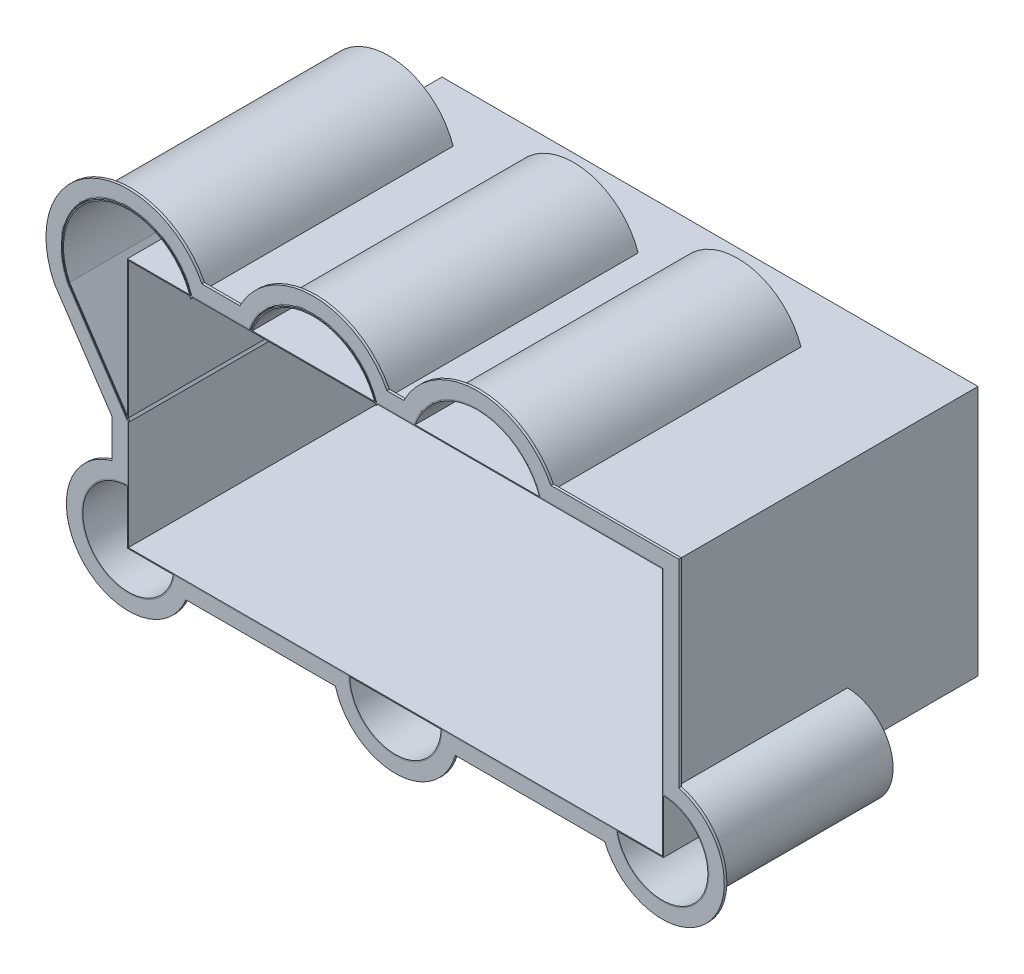
SolidWorks part; units mm, degrees
ref_plane "Front Plane" through (0, 0, 0) normal (0, 0, 1) x (1, 0, 0)
ref_plane "Top Plane" through (0, 0, 0) normal (0, 1, 0) x (1, 0, 0)
ref_plane "Right Plane" through (0, 0, 0) normal (1, 0, 0) x (0, 0, -1)
sketch "body " plane through (0, 0, 0) normal (0, 0, 1) x (1, 0, 0)
  line L0 (-4198.5075, 0) -> (2630, 0) construction
  line L1 (0, 1904.4776) -> (0, 1377) construction
  line L2 (-182.0761, 1377) -> (182.0761, 1377) construction
  line L3 (-2004.5761, 1377) -> (-1432.9239, 1377) construction
  line L4 (-2642, 0) -> (-2642, -552.1829) construction
  line L5 (-2174.5168, -1097) -> (-461.8441, -1097) construction
  line L6 (2642, 1377) -> (2642, -552.1829) construction
  line L7 (1432.9239, 1377) -> (2642, 1377) construction
  line L8 (461.8441, -1097) -> (2174.5168, -1097) construction
  line L9 (-3228.6495, 877.4) -> (-2642, 0) construction
  line L10 (-3359.2206, 802.8148) -> (-2792, -45.5271)
  line L11 (-2792, -45.5271) -> (-2792, -424.1059)
  line L12 (-2063.0892, -1247) -> (-590.1695, -1247)
  line L13 (590.1695, -1247) -> (2063.0892, -1247)
  line L14 (2792, 1527) -> (2792, -424.1059)
  line L15 (1531.8307, 1527) -> (2792, 1527)
  line L16 (-83.1693, 1527) -> (83.1693, 1527)
  line L17 (-1905.6693, 1527) -> (-1531.8307, 1527)
  line L18 (-4764.719, 1972) -> (6902.6993, 1972) construction
  line L19 (0, -1697) -> (4849.5432, -1697) construction
  line L20 (-4553.6407, -1626) -> (3482.8368, -1626) construction
  line L21 (-3442, 2950.9542) -> (-3442, -552.1829) construction
  line L22 (-2184.6364, -1085) -> (-450, -1085)
  line L23 (450, -1085) -> (2184.6364, -1085)
  line L24 (2630, 1365) -> (2630, -564.0011)
  line L25 (1424.3266, 1365) -> (2630, 1365)
  line L26 (-190.6734, 1365) -> (190.6734, 1365)
  line L27 (-2013.1734, 1365) -> (-1424.3266, 1365)
  line L28 (-3218.1761, 883.3254) -> (-2630, 3.6422)
  line L29 (-2630, 3.6422) -> (-2630, -564.0011)
  line L30 (-2630, 3.6422) -> (-2630, 1365) construction
  line L31 (-2630, -564.0011) -> (-2630, -1085) construction
  line L32 (-2630, -1085) -> (-2184.6364, -1085) construction
  line L33 (-2630, 1365) -> (2792, 1365) construction
  line L34 (2184.6364, -1085) -> (2630, -1085) construction
  line L35 (2630, -1085) -> (2630, -564.0011) construction
  line L36 (0, 1365) -> (0, -1535) construction
  line L37 (2642, 0) -> (4111.9403, 0) construction
  line L38 (0, -1547) -> (0, -2034.3284) construction
  line L39 (-2640, 0.607) -> (-2640, -554.1315)
  line L40 (-2176.1877, -1095) -> (-459.8913, -1095)
  line L41 (459.8913, -1095) -> (2176.1877, -1095)
  line L42 (2640, 1375) -> (2640, -554.1315)
  line L43 (1431.4992, 1375) -> (2640, 1375)
  line L44 (-183.5008, 1375) -> (183.5008, 1375)
  line L45 (-2006.0008, 1375) -> (-1431.4992, 1375)
  line L46 (-3226.9043, 878.388) -> (-2640, 0.607)
  line L51 (-450, -1085) -> (450, -1085) construction
  arc A0 (-182.0761, 1377) -> (-1432.9239, 1377) centre (-807.5, 1160) ccw construction
  arc A1 (1432.9239, 1377) -> (182.0761, 1377) centre (807.5, 1160) ccw construction
  arc A2 (-2642, -552.1829) -> (-2174.5168, -1097) centre (-2629, -1014) ccw construction
  arc A3 (-461.8441, -1097) -> (461.8441, -1097) centre (0, -1085) ccw construction
  arc A4 (2174.5168, -1097) -> (2642, -552.1829) centre (2629, -1014) ccw construction
  arc A5 (-2004.5761, 1377) -> (-3228.6495, 877.4) centre (-2630, 1160) ccw construction
  arc A6 (-1905.6693, 1527) -> (-3359.2206, 802.8148) centre (-2630, 1160) ccw
  arc A7 (-2792, -424.1059) -> (-2063.0892, -1247) centre (-2629, -1014) ccw
  arc A8 (-590.1695, -1247) -> (590.1695, -1247) centre (0, -1085) ccw
  arc A9 (2063.0892, -1247) -> (2792, -424.1059) centre (2629, -1014) ccw
  arc A10 (1531.8307, 1527) -> (83.1693, 1527) centre (807.5, 1160) ccw
  arc A11 (-83.1693, 1527) -> (-1531.8307, 1527) centre (-807.5, 1160) ccw
  arc A12 (-2630, -564.0011) -> (-2184.6364, -1085) centre (-2629, -1014) ccw
  arc A13 (-450, -1085) -> (450, -1085) centre (0, -1085) ccw
  arc A14 (2184.6364, -1085) -> (2630, -564.0011) centre (2629, -1014) ccw
  arc A15 (1424.3266, 1365) -> (190.6734, 1365) centre (807.5, 1160) ccw
  arc A16 (-190.6734, 1365) -> (-1424.3266, 1365) centre (-807.5, 1160) ccw
  arc A17 (-2013.1734, 1365) -> (-3218.1761, 883.3254) centre (-2630, 1160) ccw
  arc A18 (-2640, -554.1315) -> (-2176.1877, -1095) centre (-2629, -1014) ccw
  arc A19 (-459.8913, -1095) -> (459.8913, -1095) centre (0, -1085) ccw
  arc A20 (2176.1877, -1095) -> (2640, -554.1315) centre (2629, -1014) ccw
  arc A21 (1431.4992, 1375) -> (183.5008, 1375) centre (807.5, 1160) ccw
  arc A22 (-183.5008, 1375) -> (-1431.4992, 1375) centre (-807.5, 1160) ccw
  arc A23 (-2006.0008, 1375) -> (-3226.9043, 878.388) centre (-2630, 1160) ccw
  dimension "D2" = 662
  dimension "D3" = 662
  dimension "D11" = 462
  dimension "D15" = 462
  dimension "D17" = 462
  dimension "D25" = 662
  dimension "D41" = 612
  dimension "D54" = 450
  dimension "D57" = 450
  dimension "D58" = 450
  dimension "D59" = 650
  dimension "D60" = 650
  dimension "D1" = 1160
  dimension "D4" = 807.5
  dimension "D5" = 807.5
  dimension "D6" = 1377
  dimension "D7" = 1834.5
  dimension "D8" = 1209.0761
  dimension "D9" = 1097
  dimension "D10" = 1014
  dimension "D12" = 2629
  dimension "D13" = 2629
  dimension "D14" = 2642
  dimension "D16" = 1085
  dimension "D18" = 461.8441
  dimension "D19" = 461.8441
  dimension "D20" = 364.1523
  dimension "D21" = 552.1829
  dimension "D22" = 1712.6726
  dimension "D23" = 1712.6726
  dimension "D24" = 1822.5
  dimension "D26" = 282.6
  dimension "D27" = 598.6495
  dimension "D28" = 1055.4565
  dimension "D29" = 552.1829
  dimension "D30" = 217
  dimension "D31" = 571.6523
  dimension "D33" = 1697
  dimension "D34" = 1626
  dimension "D35" = 1972
  dimension "D36" = 3598
  dimension "D37" = 1972
  dimension "D38" = 1626
  dimension "D39" = 3669
  dimension "D40" = 6234
  dimension "D42" = 83
  dimension "D43" = 1472.9198
  dimension "D44" = 1472.9198
  dimension "D45" = 424.1059
  dimension "D46" = 1951.1059
  dimension "D47" = 1260.1693
  dimension "D48" = 166.3385
  dimension "D49" = 373.8385
  dimension "D50" = 1020.5015
  dimension "D51" = 2642
  dimension "D52" = 1014
  dimension "D55" = 2630
  dimension "D56" = 2630
  dimension "D61" = 1365
  dimension "D62" = 33.768
  dimension "D63" = 1085
  dimension "D64" = 10
  dimension "D32" = 150
  dimension "D53" = 12
sketch "curb" plane through (0, 0, 0) normal (0, 0, 1) x (1, 0, 0)
  line L0 (-4198.5075, 0) -> (2630, 0) construction
  line L1 (0, 1904.4776) -> (0, 1377) construction
  line L2 (-182.0761, 1377) -> (182.0761, 1377) construction
  line L3 (-2004.5761, 1377) -> (-1432.9239, 1377) construction
  line L4 (-2642, 0) -> (-2642, -552.1829) construction
  line L5 (-2174.5168, -1097) -> (-461.8441, -1097) construction
  line L6 (2642, 1377) -> (2642, -552.1829) construction
  line L7 (1432.9239, 1377) -> (2642, 1377) construction
  line L8 (461.8441, -1097) -> (2174.5168, -1097) construction
  line L9 (-3228.6495, 877.4) -> (-2642, 0) construction
  line L10 (-3359.2206, 802.8148) -> (-2792, -45.5271)
  line L11 (-2792, -45.5271) -> (-2792, -424.1059)
  line L12 (-2063.0892, -1247) -> (-590.1695, -1247)
  line L13 (590.1695, -1247) -> (2063.0892, -1247)
  line L14 (2792, 1527) -> (2792, -424.1059)
  line L15 (1531.8307, 1527) -> (2792, 1527)
  line L16 (-83.1693, 1527) -> (83.1693, 1527)
  line L17 (-1905.6693, 1527) -> (-1531.8307, 1527)
  line L18 (-4764.719, 1972) -> (6902.6993, 1972) construction
  line L19 (0, -1697) -> (4849.5432, -1697) construction
  line L20 (-4553.6407, -1626) -> (3482.8368, -1626) construction
  line L21 (-3442, 2950.9542) -> (-3442, -552.1829) construction
  line L22 (-2184.6364, -1085) -> (-450, -1085)
  line L23 (450, -1085) -> (2184.6364, -1085)
  line L24 (2630, 1365) -> (2630, -564.0011)
  line L25 (1424.3266, 1365) -> (2630, 1365)
  line L26 (-190.6734, 1365) -> (190.6734, 1365)
  line L27 (-2013.1734, 1365) -> (-1424.3266, 1365)
  line L28 (-3218.1761, 883.3254) -> (-2630, 3.6422)
  line L29 (-2630, 3.6422) -> (-2630, -564.0011)
  line L30 (-2630, 3.6422) -> (-2630, 1365) construction
  line L31 (-2630, -564.0011) -> (-2630, -1085) construction
  line L32 (-2630, -1085) -> (-2184.6364, -1085) construction
  line L33 (-2630, 1365) -> (2792, 1365) construction
  line L34 (2184.6364, -1085) -> (2630, -1085) construction
  line L35 (2630, -1085) -> (2630, -564.0011) construction
  line L36 (0, 1365) -> (0, -1535) construction
  line L37 (2642, 0) -> (4111.9403, 0) construction
  line L38 (0, -1547) -> (0, -2034.3284) construction
  line L39 (-2640, 0.607) -> (-2640, -554.1315)
  line L40 (-2176.1877, -1095) -> (-459.8913, -1095)
  line L41 (459.8913, -1095) -> (2176.1877, -1095)
  line L42 (2640, 1375) -> (2640, -554.1315)
  line L43 (1431.4992, 1375) -> (2640, 1375)
  line L44 (-183.5008, 1375) -> (183.5008, 1375)
  line L45 (-2006.0008, 1375) -> (-1431.4992, 1375)
  line L46 (-3226.9043, 878.388) -> (-2640, 0.607)
  line L47 (0, 0) -> (270.3964, 194.0028)
  line L48 (270.3964, 194.0028) -> (0, 194.0028)
  line L49 (0, 194.0028) -> (270.3964, 0)
  line L50 (270.3964, 0) -> (270.3964, 194.0028)
  arc A0 (-182.0761, 1377) -> (-1432.9239, 1377) centre (-807.5, 1160) ccw construction
  arc A1 (1432.9239, 1377) -> (182.0761, 1377) centre (807.5, 1160) ccw construction
  arc A2 (-2642, -552.1829) -> (-2174.5168, -1097) centre (-2629, -1014) ccw construction
  arc A3 (-461.8441, -1097) -> (461.8441, -1097) centre (0, -1085) ccw construction
  arc A4 (2174.5168, -1097) -> (2642, -552.1829) centre (2629, -1014) ccw construction
  arc A5 (-2004.5761, 1377) -> (-3228.6495, 877.4) centre (-2630, 1160) ccw construction
  arc A6 (-1905.6693, 1527) -> (-3359.2206, 802.8148) centre (-2630, 1160) ccw
  arc A7 (-2792, -424.1059) -> (-2063.0892, -1247) centre (-2629, -1014) ccw
  arc A8 (-590.1695, -1247) -> (590.1695, -1247) centre (0, -1085) ccw
  arc A9 (2063.0892, -1247) -> (2792, -424.1059) centre (2629, -1014) ccw
  arc A10 (1531.8307, 1527) -> (83.1693, 1527) centre (807.5, 1160) ccw
  arc A11 (-83.1693, 1527) -> (-1531.8307, 1527) centre (-807.5, 1160) ccw
  arc A12 (-2630, -564.0011) -> (-2184.6364, -1085) centre (-2629, -1014) ccw
  arc A13 (-450, -1085) -> (450, -1085) centre (0, -1085) ccw
  arc A14 (2184.6364, -1085) -> (2630, -564.0011) centre (2629, -1014) ccw
  arc A15 (1424.3266, 1365) -> (190.6734, 1365) centre (807.5, 1160) ccw
  arc A16 (-190.6734, 1365) -> (-1424.3266, 1365) centre (-807.5, 1160) ccw
  arc A17 (-2013.1734, 1365) -> (-3218.1761, 883.3254) centre (-2630, 1160) ccw
  arc A18 (-2640, -554.1315) -> (-2176.1877, -1095) centre (-2629, -1014) ccw
  arc A19 (-459.8913, -1095) -> (459.8913, -1095) centre (0, -1085) ccw
  arc A20 (2176.1877, -1095) -> (2640, -554.1315) centre (2629, -1014) ccw
  arc A21 (1431.4992, 1375) -> (183.5008, 1375) centre (807.5, 1160) ccw
  arc A22 (-183.5008, 1375) -> (-1431.4992, 1375) centre (-807.5, 1160) ccw
  arc A23 (-2006.0008, 1375) -> (-3226.9043, 878.388) centre (-2630, 1160) ccw
  point P107 (0, 0)
  dimension "D2" = 662
  dimension "D3" = 662
  dimension "D11" = 462
  dimension "D15" = 462
  dimension "D17" = 462
  dimension "D25" = 662
  dimension "D41" = 612
  dimension "D54" = 450
  dimension "D57" = 450
  dimension "D58" = 450
  dimension "D59" = 650
  dimension "D60" = 650
  dimension "D1" = 1160
  dimension "D4" = 807.5
  dimension "D5" = 807.5
  dimension "D6" = 1377
  dimension "D7" = 1834.5
  dimension "D8" = 1209.0761
  dimension "D9" = 1097
  dimension "D10" = 1014
  dimension "D12" = 2629
  dimension "D13" = 2629
  dimension "D14" = 2642
  dimension "D16" = 1085
  dimension "D18" = 461.8441
  dimension "D19" = 461.8441
  dimension "D20" = 364.1523
  dimension "D21" = 552.1829
  dimension "D22" = 1712.6726
  dimension "D23" = 1712.6726
  dimension "D24" = 1822.5
  dimension "D26" = 282.6
  dimension "D27" = 598.6495
  dimension "D28" = 1055.4565
  dimension "D29" = 552.1829
  dimension "D30" = 217
  dimension "D31" = 571.6523
  dimension "D33" = 1697
  dimension "D34" = 1626
  dimension "D35" = 1972
  dimension "D36" = 3598
  dimension "D37" = 1972
  dimension "D38" = 1626
  dimension "D39" = 3669
  dimension "D40" = 6234
  dimension "D42" = 83
  dimension "D43" = 1472.9198
  dimension "D44" = 1472.9198
  dimension "D45" = 424.1059
  dimension "D46" = 1951.1059
  dimension "D47" = 1260.1693
  dimension "D48" = 166.3385
  dimension "D49" = 373.8385
  dimension "D50" = 1020.5015
  dimension "D51" = 2642
  dimension "D52" = 1014
  dimension "D55" = 2630
  dimension "D56" = 2630
  dimension "D61" = 1365
  dimension "D62" = 33.768
  dimension "D63" = 1085
  dimension "D64" = 10
  dimension "D65" = 270.3964
  dimension "D66" = 194.0028
  dimension "D32" = 150
  dimension "D53" = 12
extrude "Boss-Extrude2" add sketch "curb" against normal blind 25 contours L16 A11 L17 A6 L10 L11 A7 L12 A8 L13 A9 L14 L15 A10 A23 L45 A22 L44 A21 L43 L42 A20 L41 A19 L40 A18 L39 L46 region at (-2958.103, 1818.5533, 0)
sketch "Sketch13" plane through (0, 0, 0) normal (0, 0, 1) x (1, 0, 0)
  line L0 (0, 6456.4078) -> (0, -8629.6869) construction
  line L1 (-8844.5601, 0) -> (9391.7632, 0) construction
  line L3 (-2630, 1365) -> (2630, 1365)
  line L4 (-2630, 1365) -> (-2630, -1085)
  line L5 (-2630, -1085) -> (2630, -1085)
  line L6 (2630, 1365) -> (2630, -1085)
  point P9 (5506.4813, -4044.3542)
  dimension "D1" = 2630
  dimension "D2" = 2630
  dimension "D3" = 1365
  dimension "D4" = 1085
  dimension "D5" = 2450
extrude "Extrude-Thin3" add sketch "Sketch13" against normal blind 3100 separate body thin thin type one direction wall 10
sketch "hv round" plane through (0, 0, 0) normal (0, 0, 1) x (1, 0, 0)
  line L0 (-4198.5075, 0) -> (2630, 0) construction
  line L1 (0, 1904.4776) -> (0, 1377) construction
  line L2 (-182.0761, 1377) -> (182.0761, 1377) construction
  line L3 (-2004.5761, 1377) -> (-1432.9239, 1377) construction
  line L4 (-2642, 0) -> (-2642, -552.1829) construction
  line L5 (-2174.5168, -1097) -> (-461.8441, -1097) construction
  line L6 (2642, 1377) -> (2642, -552.1829) construction
  line L7 (1432.9239, 1377) -> (2642, 1377) construction
  line L8 (461.8441, -1097) -> (2174.5168, -1097) construction
  line L18 (-4764.719, 1972) -> (6902.6993, 1972) construction
  line L19 (0, -1697) -> (4849.5432, -1697) construction
  line L20 (-4553.6407, -1626) -> (3482.8368, -1626) construction
  line L21 (-3442, 2950.9542) -> (-3442, -552.1829) construction
  line L22 (-2184.6364, -1085) -> (-450, -1085) construction
  line L23 (450, -1085) -> (2184.6364, -1085) construction
  line L24 (2630, 1365) -> (2630, -564.0011) construction
  line L25 (1424.3266, 1365) -> (2630, 1365) construction
  line L26 (-190.6734, 1365) -> (190.6734, 1365) construction
  line L27 (-2013.1734, 1365) -> (-1424.3266, 1365) construction
  line L29 (-2630, 3.6422) -> (-2630, -564.0011) construction
  line L30 (-2630, 3.6422) -> (-2630, 1365) construction
  line L31 (-2630, -564.0011) -> (-2630, -1085) construction
  line L32 (-2630, -1085) -> (-2184.6364, -1085) construction
  line L33 (-2630, 1365) -> (2642, 1365) construction
  line L34 (2184.6364, -1085) -> (2630, -1085) construction
  line L35 (2630, -1085) -> (2630, -564.0011) construction
  line L36 (0, 1365) -> (0, -1535) construction
  line L37 (2642, 0) -> (4111.9403, 0) construction
  line L38 (0, -1547) -> (0, -2034.3284) construction
  line L39 (-2640, 0.607) -> (-2640, -554.1315) construction
  line L40 (-2176.1877, -1095) -> (-459.8913, -1095) construction
  line L41 (459.8913, -1095) -> (2176.1877, -1095) construction
  line L42 (2640, 1375) -> (2640, -554.1315) construction
  line L43 (1431.4992, 1375) -> (2640, 1375) construction
  line L44 (-183.5008, 1375) -> (183.5008, 1375) construction
  line L45 (-2006.0008, 1375) -> (-1431.4992, 1375) construction
  line L47 (-2006.0008, 1375) -> (-2013.1734, 1365)
  line L51 (-450, -1085) -> (450, -1085) construction
  line L52 (-2640, 0.607) -> (-2630, 3.6422)
  line L53 (-190.6734, 1365) -> (-183.5008, 1375)
  line L54 (2184.6364, -1085) -> (2176.1877, -1095)
  line L55 (2630, -564.0011) -> (2640, -554.1315)
  line L56 (459.8913, -1095) -> (450, -1085)
  line L57 (-459.8913, -1095) -> (-450, -1085)
  line L58 (-2176.1877, -1095) -> (-2184.6364, -1085)
  line L59 (-2630, -564.0011) -> (-2640, -554.1315)
  line L61 (-3218.1761, 883.3254) -> (-2630, 3.6422) construction
  line L62 (-3226.9043, 878.388) -> (-2640, 0.607) construction
  line L63 (-3228.6495, 877.4) -> (-2642, 0) construction
  arc A2 (-2642, -552.1829) -> (-2174.5168, -1097) centre (-2629, -1014) ccw construction
  arc A3 (-461.8441, -1097) -> (461.8441, -1097) centre (0, -1085) ccw construction
  arc A4 (2174.5168, -1097) -> (2642, -552.1829) centre (2629, -1014) ccw construction
  arc A12 (-2630, -564.0011) -> (-2184.6364, -1085) centre (-2629, -1014) ccw
  arc A13 (-450, -1085) -> (450, -1085) centre (0, -1085) ccw
  arc A14 (2184.6364, -1085) -> (2630, -564.0011) centre (2629, -1014) ccw
  arc A18 (-2640, -554.1315) -> (-2176.1877, -1095) centre (-2629, -1014) ccw
  arc A19 (-459.8913, -1095) -> (459.8913, -1095) centre (0, -1085) ccw
  arc A20 (2176.1877, -1095) -> (2640, -554.1315) centre (2629, -1014) ccw
  arc A24 (-2013.1734, 1365) -> (-3218.1761, 883.3254) centre (-2630, 1160) ccw construction
  arc A25 (-2006.0008, 1375) -> (-3226.9043, 878.388) centre (-2630, 1160) ccw construction
  arc A26 (-2004.5761, 1377) -> (-3228.6495, 877.4) centre (-2630, 1160) ccw construction
  arc A27 (-190.6734, 1365) -> (-1424.3266, 1365) centre (-807.5, 1160) ccw construction
  arc A28 (-183.5008, 1375) -> (-1431.4992, 1375) centre (-807.5, 1160) ccw construction
  arc A29 (-182.0761, 1377) -> (-1432.9239, 1377) centre (-807.5, 1160) ccw construction
  arc A30 (1424.3266, 1365) -> (190.6734, 1365) centre (807.5, 1160) ccw construction
  arc A31 (1431.4992, 1375) -> (183.5008, 1375) centre (807.5, 1160) ccw construction
  arc A32 (1432.9239, 1377) -> (182.0761, 1377) centre (807.5, 1160) ccw construction
  dimension "D11" = 462
  dimension "D15" = 462
  dimension "D17" = 462
  dimension "D54" = 450
  dimension "D57" = 450
  dimension "D58" = 450
  dimension "D6" = 1377
  dimension "D8" = 1209.0761
  dimension "D9" = 1097
  dimension "D10" = 1014
  dimension "D12" = 2629
  dimension "D13" = 2629
  dimension "D14" = 2642
  dimension "D16" = 1085
  dimension "D18" = 461.8441
  dimension "D19" = 461.8441
  dimension "D20" = 364.1523
  dimension "D21" = 552.1829
  dimension "D22" = 1712.6726
  dimension "D23" = 1712.6726
  dimension "D29" = 552.1829
  dimension "D31" = 571.6523
  dimension "D33" = 1697
  dimension "D34" = 1626
  dimension "D35" = 1972
  dimension "D36" = 3598
  dimension "D37" = 1972
  dimension "D38" = 1626
  dimension "D39" = 3669
  dimension "D42" = 83
  dimension "D51" = 2642
  dimension "D52" = 1014
  dimension "D55" = 2630
  dimension "D56" = 2630
  dimension "D61" = 1365
  dimension "D63" = 1085
  dimension "D64" = 10
  dimension "D53" = 12
sketch "oltc round" plane through (0, 0, 0) normal (0, 0, 1) x (1, 0, 0)
  line L0 (-4198.5075, 0) -> (2630, 0) construction
  line L1 (0, 1904.4776) -> (0, 1377) construction
  line L2 (-182.0761, 1377) -> (182.0761, 1377) construction
  line L3 (-2004.5761, 1377) -> (-1432.9239, 1377) construction
  line L4 (-2642, 0) -> (-2642, -552.1829) construction
  line L5 (-2174.5168, -1097) -> (-461.8441, -1097) construction
  line L6 (2642, 1377) -> (2642, -552.1829) construction
  line L7 (1432.9239, 1377) -> (2642, 1377) construction
  line L8 (461.8441, -1097) -> (2174.5168, -1097) construction
  line L9 (-3228.6495, 877.4) -> (-2642, 0) construction
  line L18 (-4764.719, 1972) -> (6902.6993, 1972) construction
  line L19 (0, -1697) -> (4849.5432, -1697) construction
  line L20 (-4553.6407, -1626) -> (3482.8368, -1626) construction
  line L21 (-3442, 2950.9542) -> (-3442, -552.1829) construction
  line L22 (-2184.6364, -1085) -> (-450, -1085) construction
  line L23 (450, -1085) -> (2184.6364, -1085) construction
  line L24 (2630, 1365) -> (2630, -564.0011) construction
  line L25 (1424.3266, 1365) -> (2630, 1365) construction
  line L26 (-190.6734, 1365) -> (190.6734, 1365) construction
  line L27 (-2013.1734, 1365) -> (-1424.3266, 1365) construction
  line L28 (-3218.1761, 883.3254) -> (-2630, 3.6422)
  line L29 (-2630, 3.6422) -> (-2630, -564.0011) construction
  line L30 (-2630, 3.6422) -> (-2630, 1365) construction
  line L31 (-2630, -564.0011) -> (-2630, -1085) construction
  line L32 (-2630, -1085) -> (-2184.6364, -1085) construction
  line L33 (-2630, 1365) -> (2642, 1365) construction
  line L34 (2184.6364, -1085) -> (2630, -1085) construction
  line L35 (2630, -1085) -> (2630, -564.0011) construction
  line L36 (0, 1365) -> (0, -1085) construction
  line L37 (2642, 0) -> (4111.9403, 0) construction
  line L38 (0, -1547) -> (0, -2034.3284) construction
  line L39 (-2640, 0.607) -> (-2640, -554.1315) construction
  line L40 (-2176.1877, -1095) -> (-459.8913, -1095) construction
  line L41 (459.8913, -1095) -> (2176.1877, -1095) construction
  line L42 (2640, 1375) -> (2640, -554.1315) construction
  line L43 (1431.4992, 1375) -> (2640, 1375) construction
  line L44 (-183.5008, 1375) -> (183.5008, 1375) construction
  line L45 (-2006.0008, 1375) -> (-1431.4992, 1375) construction
  line L46 (-3226.9043, 878.388) -> (-2640, 0.607)
  line L47 (-2006.0008, 1375) -> (-2013.1734, 1365)
  line L51 (-450, -1085) -> (450, -1085) construction
  line L52 (-2640, 0.607) -> (-2630, 3.6422)
  line L53 (-190.6734, 1365) -> (-183.5008, 1375)
  line L54 (2184.6364, -1085) -> (2176.1877, -1095)
  line L55 (2630, -564.0011) -> (2640, -554.1315)
  line L56 (459.8913, -1095) -> (450, -1085)
  line L57 (-459.8913, -1095) -> (-450, -1085)
  line L58 (-2176.1877, -1095) -> (-2184.6364, -1085)
  line L59 (-2630, -564.0011) -> (-2640, -554.1315)
  arc A0 (-182.0761, 1377) -> (-1432.9239, 1377) centre (-807.5, 1160) ccw construction
  arc A1 (1432.9239, 1377) -> (182.0761, 1377) centre (807.5, 1160) ccw construction
  arc A5 (-2004.5761, 1377) -> (-3228.6495, 877.4) centre (-2630, 1160) ccw construction
  arc A15 (1424.3266, 1365) -> (190.6734, 1365) centre (807.5, 1160) ccw
  arc A16 (-190.6734, 1365) -> (-1424.3266, 1365) centre (-807.5, 1160) ccw
  arc A17 (-2013.1734, 1365) -> (-3218.1761, 883.3254) centre (-2630, 1160) ccw
  arc A21 (1431.4992, 1375) -> (183.5008, 1375) centre (807.5, 1160) ccw
  arc A22 (-183.5008, 1375) -> (-1431.4992, 1375) centre (-807.5, 1160) ccw
  arc A23 (-2006.0008, 1375) -> (-3226.9043, 878.388) centre (-2630, 1160) ccw
  arc A24 (-2642, -552.1829) -> (-2174.5168, -1097) centre (-2629, -1014) ccw construction
  arc A25 (-2640, -554.1315) -> (-2176.1877, -1095) centre (-2629, -1014) ccw construction
  arc A26 (-2630, -564.0011) -> (-2184.6364, -1085) centre (-2629, -1014) ccw construction
  arc A27 (-461.8441, -1097) -> (461.8441, -1097) centre (0, -1085) ccw construction
  arc A28 (-459.8913, -1095) -> (459.8913, -1095) centre (0, -1085) ccw construction
  arc A29 (-450, -1085) -> (450, -1085) centre (0, -1085) ccw construction
  arc A30 (2174.5168, -1097) -> (2642, -552.1829) centre (2629, -1014) ccw construction
  arc A31 (2176.1877, -1095) -> (2640, -554.1315) centre (2629, -1014) ccw construction
  arc A32 (2184.6364, -1085) -> (2630, -564.0011) centre (2629, -1014) ccw construction
  dimension "D2" = 662
  dimension "D3" = 662
  dimension "D25" = 662
  dimension "D59" = 650
  dimension "D60" = 650
  dimension "D1" = 1160
  dimension "D4" = 807.5
  dimension "D5" = 807.5
  dimension "D6" = 1377
  dimension "D7" = 1834.5
  dimension "D8" = 1209.0761
  dimension "D9" = 1097
  dimension "D14" = 2642
  dimension "D18" = 461.8441
  dimension "D19" = 461.8441
  dimension "D20" = 364.1523
  dimension "D21" = 552.1829
  dimension "D22" = 1712.6726
  dimension "D23" = 1712.6726
  dimension "D24" = 1822.5
  dimension "D26" = 282.6
  dimension "D27" = 598.6495
  dimension "D28" = 1055.4565
  dimension "D29" = 552.1829
  dimension "D30" = 217
  dimension "D31" = 571.6523
  dimension "D33" = 1697
  dimension "D34" = 1626
  dimension "D35" = 1972
  dimension "D36" = 3598
  dimension "D37" = 1972
  dimension "D38" = 1626
  dimension "D39" = 3669
  dimension "D51" = 2642
  dimension "D55" = 2630
  dimension "D56" = 2630
  dimension "D61" = 1365
  dimension "D62" = 33.768
  dimension "D63" = 1085
  dimension "D64" = 10
  dimension "D53" = 12
extrude "oltc round-Extrude5" add sketch "hv round" against normal blind 1815 separate body contours A12 L58 A18 L59 | A13 L56 A19 L57 | A14 L55 A20 L54
extrude "Extrude-Thin6" add sketch "oltc round" against normal blind 2565 separate body thin contours A17 L28 L52 L46 A23 L47 | A22 L53 A16 | A15 thin type one direction wall 10
